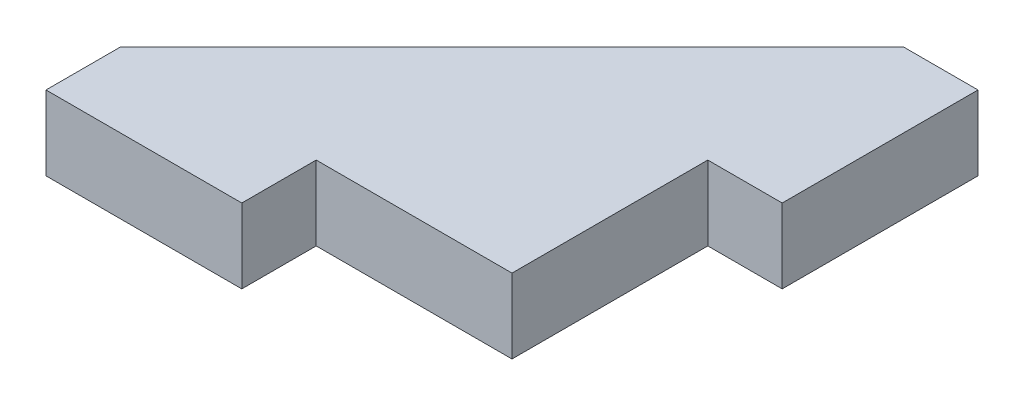
SolidWorks part; units mm, degrees
ref_plane "Front Plane" through (0, 0, 0) normal (0, 0, 1) x (1, 0, 0)
ref_plane "Top Plane" through (0, 0, 0) normal (0, 1, 0) x (1, 0, 0)
ref_plane "Right Plane" through (0, 0, 0) normal (1, 0, 0) x (0, 0, -1)
sketch "Sketch1" plane through (0, 0, 0) normal (0, 1, 0) x (1, 0, 0)
  line L0 (-21.062, -13.6221) -> (4.338, 11.7779)
  line L2 (4.338, 11.7779) -> (9.164, 11.7779)
  line L3 (-21.062, -13.6221) -> (4.338, -13.6221)
  line L4 (4.338, 11.7779) -> (4.338, -13.6221)
  line L5 (4.338, 11.7779) -> (4.338, -0.9221)
  line L6 (4.338, -0.9221) -> (9.164, -0.9221)
  line L7 (9.164, 11.7779) -> (9.164, -0.9221)
  line L8 (-21.062, -13.6221) -> (-8.362, -13.6221)
  line L9 (-21.062, -13.6221) -> (-21.062, -18.4481)
  line L10 (-21.062, -18.4481) -> (-8.362, -18.4481)
  line L11 (-8.362, -13.6221) -> (-8.362, -18.4481)
  dimension "D2" = 25.4
  dimension "D3" = 12.7
  dimension "D4" = 4.826
  dimension "D5" = 4.826
extrude "Boss-Extrude1" add sketch "Sketch1" along normal blind 4.826 contours L11 L3 L9 L10 | L4 L0 L3 | L7 L2 L4 L6 region at (-4.1287, 0, 5.1554) region at (-14.712, 0, 16.0351) region at (6.751, 0, -5.4279)
equation "\"MDF\"= 0.19in"
equation "\"Foamcore\"= .13in"
equation "\"Gmaterial\"= \"MDF\""
equation "\"D4@Sketch1\"=\"MDF\""
equation "\"D5@Sketch1\"=\"MDF\""
equation "\"D1@Boss-Extrude1\"=\"MDF\""
equation "\"PVCID\" = 2.067in"
equation "\"PVCOD\" = 2.375in"
equation "\"GenDiameter\"= 60mm"
equation "\"GenCutDiameter\" = 1.8in"
equation "\"GenCutDistance\" = 1"
equation "\"TowerHeight\" = 6in"
equation "\"TowerFrontBase\" = 3in"
equation "\"FunnelHeight\" = 1in"
equation "\"FunnelAngle\" = 20"
equation "\"TowerSideBase\" = 3in"
equation "\"TowerPanelLength\" = 2in"
equation "\"TowerPanelLeeway\" = 0.5in"
equation "\"BaseLength\" = 9in"
equation "\"BaseWidth\" = 10in"
equation "\"WheelHoleLength\" = 3.25in"
equation "\"WheelHoleWidth\" = 26mm"
equation "\"WheelHoleFromBack\" = 1.5in"
equation "\"DropLength\" = 1in"
equation "\"DropWidth\" = 8.5in"
equation "\"BumperWidth\" = 1in"
equation "\"HoleDiameter\"= 0.25in"
equation "\"SmallHexDiameter\" = 0.185in"
equation "\"SmallHexHeight\" = 0.701in"
equation "\"ScrewSize\" = 0.106in"
equation "\"BigHexDiameter\" = 0.251in"
equation "\"BigHexHeight\" = 0.374in"
equation "\"PCBThickness\" = 0.066in"
equation "\"ConnectorHeight\" = 0.517in"
equation "\"BoardHeight\" = 0.583in"
equation "\"UnoStackHeight\" = 1.351in"
equation "\"UnoStackWidth\" = 3.053in"
equation "\"UnoStackLength\" = 3.152in"
equation "\"HBridgeWidth\" = 1.797in"
equation "\"HBridgeLength\" = 2.236in"
equation "\"DSWidth\" = 1.820in"
equation "\"DSLength\" = 1.833in"
equation "\"StepperWidth\" = 1.799in"
equation "\"StepperLength\" = 2.248in"
equation "\"ULNWidth\" = 1.304in"
equation "\"ULNLength\" = 1.545in"
equation "\"VSwitchHeight\" = 0.392in"
equation "\"VSwitchWidth\" = 0.637in"
equation "\"VSwitchLength\" = 1.097in"
equation "\"SkateWheelDiameter\" = 80mm"
equation "\"SkateWheelThickness\" = 24mm"
equation "\"BaseDistance\" = 3in"
